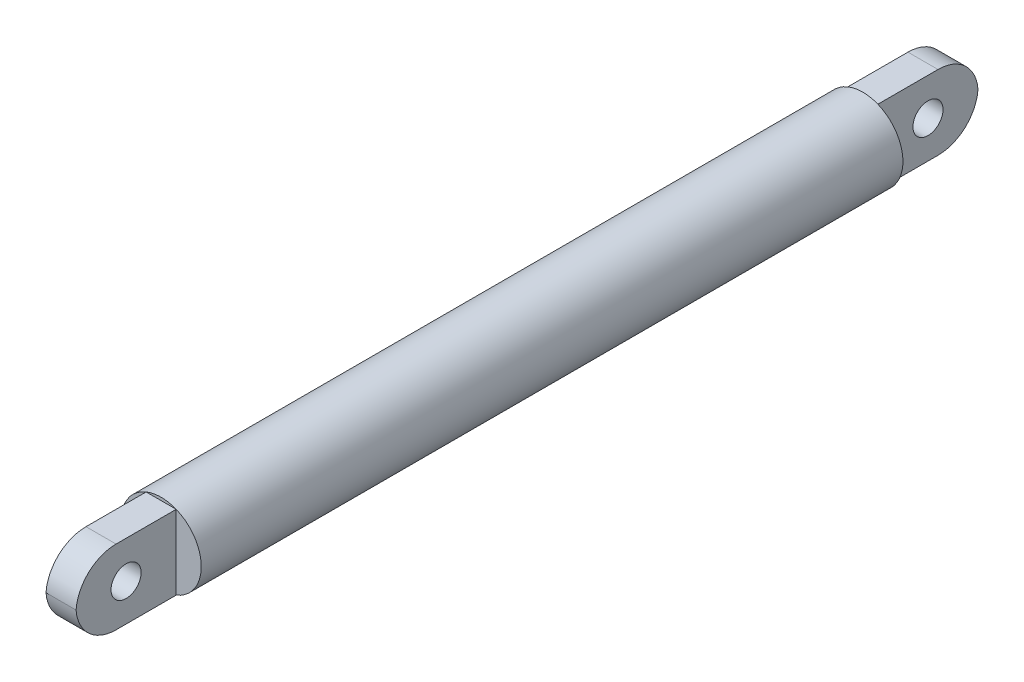
SolidWorks part; units mm, degrees
ref_plane "Alzado" through (0, 0, 0) normal (0, 0, 1) x (1, 0, 0)
ref_plane "Planta" through (0, 0, 0) normal (0, 1, 0) x (1, 0, 0)
ref_plane "Vista lateral" through (0, 0, 0) normal (1, 0, 0) x (0, 0, -1)
sketch "Croquis2" plane through (0, 0, 0) normal (0, 0, 1) x (1, 0, 0)
  circle A0 centre (0, 0) radius 4
  dimension "D1" = 8
extrude "Saliente-Extruir1" add sketch "Croquis2" along normal blind 70
sketch "Croquis3" plane through (0, 0, 70) normal (0, 0, 1) x (1, 0, 0)
  line L1 (-1.5, -3.7081) -> (1.5, -3.7081)
  line L2 (-1.5, -3.7081) -> (-1.5, 3.7081)
  line L3 (-1.5, 3.7081) -> (1.5, 3.7081)
  line L4 (1.5, -3.7081) -> (1.5, 3.7081)
  line L5 (-1.5, -3.7081) -> (1.5, 3.7081) construction
  line L6 (-1.5, 3.7081) -> (1.5, -3.7081) construction
  circle A0 centre (0, 0) radius 4
  dimension "D2" = 8
  dimension "D1" = 3
extrude "Saliente-Extruir2" add sketch "Croquis3" along normal blind 10 contours L1 L4 L3 L2 region at (0, 0, 70)
sketch "Croquis4" plane through (0, 0, 0) normal (0, 0, -1) x (-1, 0, 0)
  line L1 (1.5, -3.7081) -> (-1.5, -3.7081)
  line L2 (1.5, -3.7081) -> (1.5, 3.7081)
  line L3 (1.5, 3.7081) -> (-1.5, 3.7081)
  line L4 (-1.5, -3.7081) -> (-1.5, 3.7081)
  line L5 (1.5, -3.7081) -> (-1.5, 3.7081) construction
  line L6 (1.5, 3.7081) -> (-1.5, -3.7081) construction
  circle A0 centre (0, 0) radius 4
  dimension "D1" = 8
  dimension "D2" = 3
extrude "Saliente-Extruir3" add sketch "Croquis4" along normal blind 10 contours L4 L1 L2 L3 region at (0, 0, 0)
sketch "Croquis5" plane through (1.5, 0, 0) normal (1, 0, 0) x (0, 0, -1)
  line L0 (-70, -3.7081) -> (-70, 3.7081) construction
  line L1 (0, -3.7081) -> (0, 3.7081) construction
  circle A0 centre (-75, 0) radius 1.5
  circle A1 centre (5, 0) radius 1.5
  dimension "D1" = 3
  dimension "D2" = 3
  dimension "D3" = 5
  dimension "D4" = 5
extrude "Cortar-Extruir1" cut sketch "Croquis5" against normal through all
fillet "Redondeo1" radius 4 4 edges at (0, -3.7081, -10) (0, 3.7081, -10) (0, -3.7081, 80) (0, 3.7081, 80)
